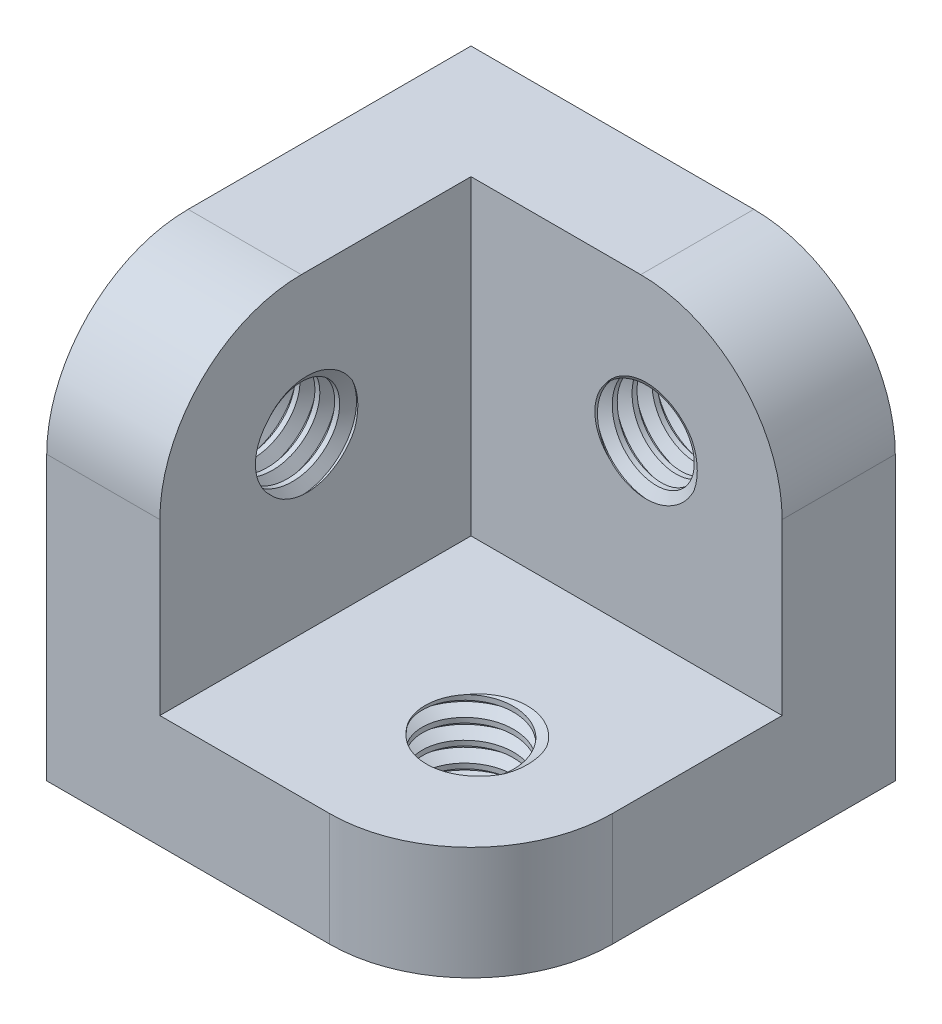
SolidWorks part; units mm, degrees
ref_plane "Front Plane" through (0, 0, 0) normal (0, 0, 1) x (1, 0, 0)
ref_plane "Top Plane" through (0, 0, 0) normal (0, 1, 0) x (1, 0, 0)
ref_plane "Right Plane" through (0, 0, 0) normal (1, 0, 0) x (0, 0, -1)
sketch "Sketch1" plane through (0, 0, 0) normal (0, 1, 0) x (1, 0, 0)
  line L1 (-7.5, -7.5) -> (7.5, -7.5)
  line L2 (-7.5, -7.5) -> (-7.5, 7.5)
  line L3 (-7.5, 7.5) -> (7.5, 7.5)
  line L4 (7.5, -7.5) -> (7.5, 7.5)
  line L5 (-7.5, -7.5) -> (7.5, 7.5) construction
  line L6 (-7.5, 7.5) -> (7.5, -7.5) construction
  point P0 (0, 0)
  dimension "D1" = 15
extrude "Boss-Extrude1" add sketch "Sketch1" along normal blind 15
sketch "Sketch2" plane through (0, 15, 0) normal (0, 1, 0) x (1, 0, 0)
  line L0 (7.5, 7.5) -> (-7.5, 7.5) construction
  line L1 (7.5, -7.5) -> (-3.5, -7.5)
  line L2 (7.5, -7.5) -> (7.5, 3.5)
  line L3 (7.5, 3.5) -> (-3.5, 3.5)
  line L4 (-3.5, -7.5) -> (-3.5, 3.5)
  dimension "D1" = 4
extrude "Cut-Extrude1" cut sketch "Sketch2" against normal offset from surface (11 mm away) 4 up to face at (0, 0, 0)
hole_wizard "Ø4.0mm Dowel Hole2" positions "3DSketch5" profile "Sketch16" hole size "Ø4.0" standard "ISO" end condition up to next
sketch3d "3DSketch5"
  line L0 (-3.5, 4, -3.5) -> (-3.5, 15, -3.5) construction
  line L1 (-3.5, 4, -3.5) -> (-3.5, 4, 7.5) construction
  line L2 (7.5, 4, -3.5) -> (-3.5, 4, -3.5) construction
  point P12 (-3.5, 10, 2.5)
  point P14 (2.5, 10, -3.5)
  point P16 (2.5, 4, 2.5)
  point P24 (0, 0, 0)
  dimension "D1" = 6
  dimension "D2" = 6
  dimension "D3" = 6
  dimension "D4" = 6
  dimension "D5" = 6
  dimension "D6" = 6
sketch "Sketch16" plane through (-3.5, 10, 2.5) normal (0, 1, 0) x (0, 0, -1)
  line L0 (0, 0) -> (0, 4)
  line L1 (0, 4) -> (2, 4)
  line L2 (2, 4) -> (2, 0)
  line L5 (2, 0) -> (0, 0)
  line L11 (0, -6.35) -> (0, 107.95) construction
  dimension "Thru Hole Dia." = 4
  dimension "Thru Hole Depth" = 4
fillet "Fillet2" radius 5 3 edges at (7.5, 2, 7.5) (7.5, 15, -5.5) (-5.5, 15, 7.5)
thread "Thread4" pitch 0.7 method extrude trim with start face yes trim with end face yes profile "Thread Profile6" start angle 0, offset 1, length 0, pitch 0.7, diameter 4
ref_plane "Plane6" through (0.5, 10, -2.5) normal (0, -1, 0) x (-1, 0, 0)
sketch "Thread Profile6" plane through (0.5, 10, -2.5) normal (0, -1, 0) x (-1, 0, 0)
  line L0 (0, 0) -> (0, 0.7) construction
  line L11 (0, 0) -> (0, 0.6125)
  line L12 (0, 0.6125) -> (-0.3789, 0.3937)
  line L13 (-0.3789, 0.3937) -> (-0.3789, 0.2187)
  line L15 (-0.3789, 0.2187) -> (0, 0)
  line L17 (-0.3789, 0.3062) -> (0, 0.3062) construction
  point P2 (0, 0)
  dimension "Pitch" = 0.7
  dimension "Profile_Angle" = 60
  dimension "Profile_Land" = 0.175
  dimension "Profile_Height" = 0.3789
thread "Thread5" pitch 0.7 method extrude trim with start face yes trim with end face yes profile "Thread Profile7" start angle 0, offset 1, length 0, pitch 0.7, diameter 4
ref_plane "Plane7" through (-2.5, 10, 4.5) normal (0, -1, 0) x (0, 0, 1)
sketch "Thread Profile7" plane through (-2.5, 10, 4.5) normal (0, -1, 0) x (0, 0, 1)
  line L0 (0, 0) -> (0, 0.7) construction
  line L11 (0, 0) -> (0, 0.6125)
  line L12 (0, 0.6125) -> (-0.3789, 0.3937)
  line L13 (-0.3789, 0.3937) -> (-0.3789, 0.2187)
  line L15 (-0.3789, 0.2187) -> (0, 0)
  line L17 (-0.3789, 0.3062) -> (0, 0.3062) construction
  point P2 (0, 0)
  dimension "Pitch" = 0.7
  dimension "Profile_Angle" = 60
  dimension "Profile_Land" = 0.175
  dimension "Profile_Height" = 0.3789
thread "Thread6" pitch 0.7 method extrude trim with start face yes trim with end face yes profile "Thread Profile8" start angle 0, offset 1, length 0, pitch 0.7, diameter 4
ref_plane "Plane8" through (0.5, 5, 2.5) normal (0, 0, 1) x (-1, 0, 0)
sketch "Thread Profile8" plane through (0.5, 5, 2.5) normal (0, 0, 1) x (-1, 0, 0)
  line L0 (0, 0) -> (0, 0.7) construction
  line L11 (0, 0) -> (0, 0.6125)
  line L12 (0, 0.6125) -> (-0.3789, 0.3937)
  line L13 (-0.3789, 0.3937) -> (-0.3789, 0.2187)
  line L15 (-0.3789, 0.2187) -> (0, 0)
  line L17 (-0.3789, 0.3062) -> (0, 0.3062) construction
  point P2 (0, 0)
  dimension "Pitch" = 0.7
  dimension "Profile_Angle" = 60
  dimension "Profile_Land" = 0.175
  dimension "Profile_Height" = 0.3789
